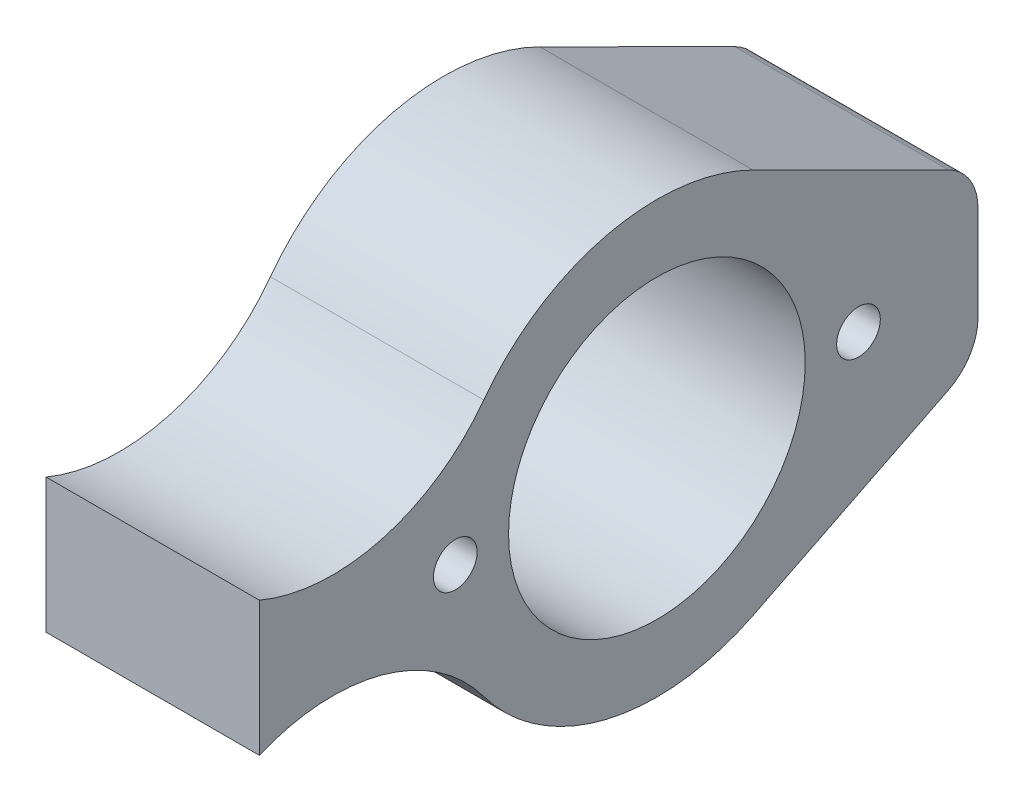
SolidWorks part; units mm, degrees
material "AISI Type A2 Tool Steel"
ref_plane "Front Plane" through (0, 0, 0) normal (0, 0, 1) x (1, 0, 0)
ref_plane "Top Plane" through (0, 0, 0) normal (0, 1, 0) x (1, 0, 0)
ref_plane "Right Plane" through (0, 0, 0) normal (1, 0, 0) x (0, 0, -1)
sketch "Sketch1" plane through (0, 0, 0) normal (1, 0, 0) x (0, 0, -1)
  line L0 (-29.5804, 5) -> (-29.5804, -5)
  line L1 (7.1611, 14.3499) -> (21.6793, 7.1048)
  line L2 (23.8932, 3.5257) -> (23.8932, -3.5257)
  line L3 (21.6793, -7.1048) -> (7.1611, -14.3499)
  line L4 (-15, 0) -> (15, 0) construction
  circle A0 centre (0, 0) radius 11.0375
  arc A1 (-29.5804, 5) -> (-12.8813, 9.5538) centre (-24.126, 17.8938) ccw
  arc A2 (-12.8813, 9.5538) -> (7.1611, 14.3499) centre (0, 0) cw
  arc A3 (-29.5804, -5) -> (-12.8813, -9.5538) centre (-24.126, -17.8938) cw
  arc A4 (-12.8813, -9.5538) -> (7.1611, -14.3499) centre (0, 0) ccw
  arc A5 (23.8932, -3.5257) -> (21.6793, -7.1048) centre (19.8932, -3.5257) cw
  arc A6 (21.6793, 7.1048) -> (23.8932, 3.5257) centre (19.8932, 3.5257) cw
  circle A7 centre (-15, 0) radius 1.625
  circle A8 centre (15, 0) radius 1.625
  point P13 (-29.5804, 0)
  point P14 (23.8932, 0)
  point P19 (23.8932, -6)
  point P22 (23.8932, 6)
  point P27 (0, 0)
  dimension "D1" = 22.075
  dimension "D2" = 30
  dimension "D3" = 5
  dimension "D5" = 14
  dimension "D8" = 4
  dimension "D9" = 3.25
  dimension "D4" = 10
  dimension "D6" = 24.635
  dimension "D7" = 12
  dimension "D10" = 30
extrude "Boss-Extrude1" add sketch "Sketch1" along normal mid plane 15.875
